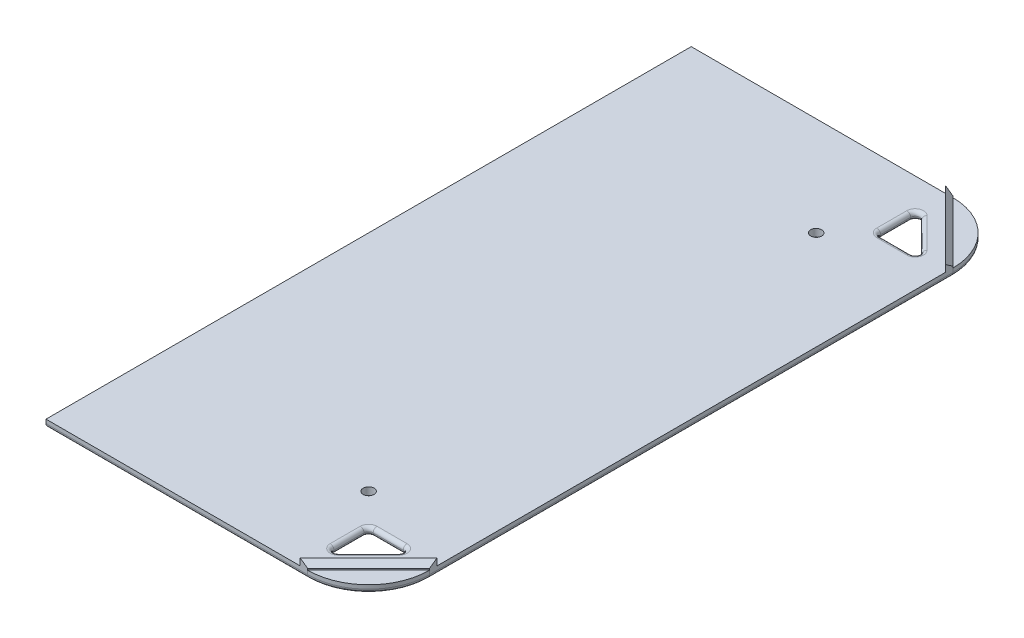
SolidWorks part; units mm, degrees
ref_plane "Front Plane" through (0, 0, 0) normal (0, 0, 1) x (1, 0, 0)
ref_plane "Top Plane" through (0, 0, 0) normal (0, 1, 0) x (1, 0, 0)
ref_plane "Right Plane" through (0, 0, 0) normal (1, 0, 0) x (0, 0, -1)
sketch "Sketch1" plane through (0, 0, 0) normal (0, 1, 0) x (1, 0, 0)
  line L0 (0, -134.62) -> (0, 134.62)
  line L1 (-134.62, -134.62) -> (134.62, -134.62)
  line L2 (-134.62, -134.62) -> (-134.62, 134.62)
  line L3 (-134.62, 134.62) -> (134.62, 134.62)
  line L4 (134.62, -134.62) -> (134.62, 134.62)
  line L5 (-134.62, -134.62) -> (134.62, 134.62) construction
  line L6 (-134.62, 134.62) -> (134.62, -134.62) construction
  point P0 (0, 0)
  point P9 (0, 0)
  dimension "D1" = 269.24
extrude "Boss-Extrude1" add sketch "Sketch1" along normal blind 3.175 contours L1 L4 L3 L0 region at (67.31, 0, 0)
sketch "Sketch2" plane through (0, 3.175, 0) normal (0, 1, 0) x (1, 0, 0)
  line L0 (109.22, 134.62) -> (134.62, 109.22)
  line L1 (109.22, 134.62) -> (106.045, 134.62)
  line L2 (106.045, 134.62) -> (134.62, 106.045)
  line L3 (134.62, 106.045) -> (134.62, 109.22)
  line L4 (0, -134.62) -> (134.62, -134.62)
  line L5 (134.62, -134.62) -> (134.62, 134.62)
  line L6 (134.62, 134.62) -> (0, 134.62)
  line L7 (0, 134.62) -> (0, -134.62)
  line L8 (0, -134.62) -> (134.62, -134.62)
  line L9 (134.62, -134.62) -> (134.62, 134.62)
  line L10 (134.62, 134.62) -> (0, 134.62)
  line L11 (0, 134.62) -> (0, -134.62)
  line L12 (109.22, -134.62) -> (134.62, -109.22)
  line L13 (134.62, -109.22) -> (134.62, -106.045)
  line L14 (134.62, -106.045) -> (106.045, -134.62)
  line L15 (106.045, -134.62) -> (109.22, -134.62)
  line L16 (120.3325, -120.3325) -> (115.3934, -115.3934)
  line L17 (120.3325, 120.3325) -> (115.3934, 115.3934)
  line L18 (105.8684, -124.9184) -> (124.9184, -105.8684)
  line L19 (124.9184, -105.8684) -> (105.8684, -105.8684)
  line L20 (105.8684, -105.8684) -> (105.8684, -124.9184)
  line L21 (124.9184, 105.8684) -> (105.8684, 124.9184)
  line L22 (105.8684, 124.9184) -> (105.8684, 105.8684)
  line L23 (105.8684, 105.8684) -> (124.9184, 105.8684)
  line L24 (120.3325, -120.3325) -> (93.3917, -93.3917)
  line L25 (120.3325, 120.3325) -> (93.3917, 93.3917)
  circle A0 centre (93.3917, -93.3917) radius 2.286
  circle A1 centre (93.3917, 93.3917) radius 2.286
  point P10 (120.3325, -120.3325)
  point P13 (120.3325, 120.3325)
  point P21 (115.3934, -115.3934)
  point P25 (115.3934, 115.3934)
  line M24 (134.62, -134.62) -> (134.62, 134.62)
  line M25 (134.62, 134.62) -> (0, 134.62)
  dimension "D17" = 4.572
  dimension "D2" = 3.175
  dimension "D3" = 25.4
  dimension "D4" = 3.175
  dimension "D5" = 25.4
  dimension "D6" = 3.175
  dimension "D7" = 3.175
  dimension "D8" = 25.4
  dimension "D9" = 6.985
  dimension "D10" = 90
  dimension "D11" = 6.985
  dimension "D12" = 90
  dimension "D13" = 19.05
  dimension "D14" = 19.05
  dimension "D15" = 38.1
  dimension "D16" = 90
  dimension "D18" = 90
  dimension "D1" = 0
extrude "Boss-Extrude2" add sketch "Sketch2" along normal blind 3.175 contours L2 L0 M25 M24 | L9 L14 L8 L12 region at (121.1107, 3.175, -121.1107) region at (121.1107, 3.175, 121.1107)
extrude "Cut-Extrude1" cut sketch "Sketch2<3>" against normal up to next contours L22 L23 L21 | A1 | L20 L18 L19 | A0
sketch "Sketch2<3>" plane through (0, 3.175, 0) normal (0, 1, 0) x (1, 0, 0) same geometry as "Sketch2"
chamfer "Chamfer1" distance 2.54 2 edges at (121.92, 6.35, 121.92) (121.92, 6.35, -121.92)
fillet "Fillet1" radius 1.905 6 edges at (105.8684, 1.5875, -105.8684) (124.9184, 1.5875, -105.8684) (105.8684, 1.5875, -124.9184) (105.8684, 1.5875, 105.8684) (105.8684, 1.5875, 124.9184) (124.9184, 1.5875, 105.8684)
fillet "Fillet2" radius 1.5875 24 edges at (107.0443, 3.175, 122.0793) (105.8684, 3.175, 114.0463) (106.4263, 3.175, 106.4263) (114.0463, 3.175, 105.8684) (122.0793, 3.175, 107.0443) (122.0793, 0, 107.0443) (114.0463, 0, 105.8684) (106.4263, 0, 106.4263) (105.8684, 0, 114.0463) (107.0443, 0, 122.0793) (122.0793, 3.175, -107.0443) (114.0463, 3.175, -105.8684) (106.4263, 3.175, -106.4263) (105.8684, 3.175, -114.0463) (107.0443, 3.175, -122.0793) (107.0443, 0, -122.0793) (105.8684, 0, -114.0463) (106.4263, 0, -106.4263) (114.0463, 0, -105.8684) (122.0793, 0, -107.0443) (115.3934, 3.175, 115.3934) (115.3934, 0, 115.3934) (115.3934, 3.175, -115.3934) (115.3934, 0, -115.3934)
fillet "Fillet3" radius 25.4 2 edges at (134.62, 1.5875, -134.62) (134.62, 1.5875, 134.62)
fillet "Fillet4" radius 1.5875 5 edges at (54.61, 0, 134.62) (127.1805, 0, 127.1805) (54.61, 0, -134.62) (127.1805, 0, -127.1805) (134.62, 0, 0)
sketch "Sketch3" plane through (0, 0, 0) normal (0, -1, 0) x (1, 0, 0)
  line L1 (0, -28.575) -> (31.75, -28.575)
  line L2 (0, -28.575) -> (0, 28.575)
  line L3 (0, 28.575) -> (31.75, 28.575)
  line L4 (109.22, 133.0325) -> (0, 133.0325)
  line L5 (0, 133.0325) -> (0, -133.0325)
  line L6 (0, -133.0325) -> (109.22, -133.0325)
  line L7 (133.0325, -109.22) -> (133.0325, 109.22)
  line L8 (109.22, 133.0325) -> (0, 133.0325)
  line L9 (0, 133.0325) -> (0, -133.0325)
  line L10 (0, -133.0325) -> (109.22, -133.0325)
  line L11 (133.0325, -109.22) -> (133.0325, 109.22)
  line L12 (31.75, -28.575) -> (31.75, 28.575)
  line L13 (0, 110.8075) -> (31.75, 110.8075)
  line L14 (0, 110.8075) -> (0, 53.6575)
  line L15 (0, 53.6575) -> (31.75, 53.6575)
  line L16 (31.75, 110.8075) -> (31.75, 53.6575)
  line L17 (0, -53.6575) -> (31.75, -53.6575)
  line L18 (0, -53.6575) -> (0, -110.8075)
  line L19 (0, -110.8075) -> (31.75, -110.8075)
  line L20 (31.75, -53.6575) -> (31.75, -110.8075)
  arc A2 (133.0325, 109.22) -> (109.22, 133.0325) centre (109.22, 109.22) ccw
  arc A3 (109.22, -133.0325) -> (133.0325, -109.22) centre (109.22, -109.22) ccw
  arc A4 (133.0325, 109.22) -> (109.22, 133.0325) centre (109.22, 109.22) ccw
  arc A5 (109.22, -133.0325) -> (133.0325, -109.22) centre (109.22, -109.22) ccw
  point P20 (0, 82.2325)
  point P21 (0, 0)
  point P22 (0, -82.2325)
  line M35 (0, 133.0325) -> (0, -133.0325)
  dimension "D2" = 57.15
  dimension "D3" = 31.75
  dimension "D4" = 50.8
  dimension "D5" = 50.8
  dimension "D1" = 0
extrude "Boss-Extrude3" add sketch "Sketch3" along normal blind 3.175 contours L16 L13 L9 L15 | L1 L12 L3 M35 | L20 L17 L9 L19 region at (15.875, 0, 0) region at (15.875, 0, -82.2325) region at (15.875, 0, 82.2325)
sketch "Sketch4" plane through (0, 0, 0) normal (-1, 0, 0) x (0, 0, 1)
  line L0 (110.8075, 0) -> (110.8075, 3.175)
  line L1 (110.8075, 3.175) -> (53.6575, 3.175)
  line L2 (53.6575, 3.175) -> (53.6575, 0)
  line L3 (28.575, 0) -> (28.575, 3.175)
  line L4 (28.575, 3.175) -> (-28.575, 3.175)
  line L5 (-28.575, 3.175) -> (-28.575, 0)
  line L6 (-53.6575, 0) -> (-53.6575, 3.175)
  line L7 (-53.6575, 3.175) -> (-110.8075, 3.175)
  line L8 (-110.8075, 3.175) -> (-110.8075, 0)
  line L9 (-53.6575, 3.175) -> (-110.8075, 3.175)
  line L10 (28.575, 3.175) -> (-28.575, 3.175)
  line L12 (-107.6325, 1.5875) -> (-56.8325, 1.5875)
  line L13 (-107.6325, 1.5875) -> (-107.6325, -1.5875)
  line L14 (-107.6325, -1.5875) -> (-56.8325, -1.5875)
  line L15 (-56.8325, 1.5875) -> (-56.8325, -1.5875)
  line L16 (110.8075, 0) -> (133.0325, 0)
  line L17 (134.62, 1.5875) -> (134.62, 3.175)
  line L18 (134.62, 3.175) -> (-134.62, 3.175)
  line L19 (-134.62, 3.175) -> (-134.62, 1.5875)
  line L20 (-133.0325, 0) -> (-110.8075, 0)
  line L21 (-110.8075, 0) -> (-110.8075, -3.175)
  line L22 (-110.8075, -3.175) -> (-53.6575, -3.175)
  line L23 (-53.6575, -3.175) -> (-53.6575, 0)
  line L24 (-53.6575, 0) -> (-28.575, 0)
  line L25 (-28.575, 0) -> (-28.575, -3.175)
  line L26 (-28.575, -3.175) -> (28.575, -3.175)
  line L27 (28.575, -3.175) -> (28.575, 0)
  line L28 (28.575, 0) -> (53.6575, 0)
  line L29 (53.6575, 0) -> (53.6575, -3.175)
  line L30 (53.6575, -3.175) -> (110.8075, -3.175)
  line L31 (110.8075, -3.175) -> (110.8075, 0)
  line L34 (110.8075, 3.175) -> (53.6575, 3.175)
  line L37 (-110.8075, 0) -> (-110.8075, -3.175)
  line L38 (-110.8075, -3.175) -> (-53.6575, -3.175)
  line L39 (-53.6575, -3.175) -> (-53.6575, 0)
  line L41 (-28.575, 0) -> (-28.575, -3.175)
  line L42 (-28.575, -3.175) -> (28.575, -3.175)
  line L43 (28.575, -3.175) -> (28.575, 0)
  line L45 (53.6575, 0) -> (53.6575, -3.175)
  line L46 (53.6575, -3.175) -> (110.8075, -3.175)
  line L47 (110.8075, -3.175) -> (110.8075, 0)
  line L48 (-107.6325, 1.5875) -> (-56.8325, -1.5875) construction
  line L49 (-107.6325, -1.5875) -> (-56.8325, 1.5875) construction
  line L50 (-25.4, 1.5875) -> (25.4, 1.5875)
  line L51 (-25.4, 1.5875) -> (-25.4, -1.5875)
  line L52 (-25.4, -1.5875) -> (25.4, -1.5875)
  line L53 (25.4, 1.5875) -> (25.4, -1.5875)
  line L54 (-25.4, 1.5875) -> (25.4, -1.5875) construction
  line L55 (-25.4, -1.5875) -> (25.4, 1.5875) construction
  line L56 (56.8325, 1.5875) -> (107.6325, 1.5875)
  line L57 (56.8325, 1.5875) -> (56.8325, -1.5875)
  line L58 (56.8325, -1.5875) -> (107.6325, -1.5875)
  line L59 (107.6325, 1.5875) -> (107.6325, -1.5875)
  line L60 (56.8325, 1.5875) -> (107.6325, -1.5875) construction
  line L61 (56.8325, -1.5875) -> (107.6325, 1.5875) construction
  arc A2 (133.0325, 0) -> (134.62, 1.5875) centre (133.0325, 1.5875) ccw
  arc A3 (-134.62, 1.5875) -> (-133.0325, 0) centre (-133.0325, 1.5875) ccw
  point P16 (82.2325, 3.175)
  point P18 (0, 3.175)
  point P20 (-82.2325, 3.175)
  point P22 (-82.2325, 0)
  point P32 (0, 0)
  point P40 (82.2325, 0)
  dimension "D2" = 50.8
  dimension "D3" = 3.175
  dimension "D1" = 0
extrude "Cut-Extrude2" cut sketch "Sketch4" against normal blind 19.05 contours L53 L50 L51 L52 | L59 L56 L57 L58 | L15 L12 L13 L14 region at (0, 0, -82.2325) region at (0, 0, 0) region at (0, 0, 82.2325)
fillet "Fillet5" radius 12.7 6 edges at (31.75, -1.5875, 110.8075) (31.75, -1.5875, 53.6575) (31.75, -1.5875, 28.575) (31.75, -1.5875, -28.575) (31.75, -1.5875, -53.6575) (31.75, -1.5875, -110.8075)
fillet "Fillet6" radius 3.175 15 edges at (9.525, -3.175, -110.8075) (28.0303, -3.175, -107.0878) (31.75, -3.175, -82.2325) (28.0303, -3.175, -57.3772) (9.525, -3.175, -28.575) (28.0303, -3.175, -24.8553) (31.75, -3.175, 0) (28.0303, -3.175, 24.8553) (9.525, -3.175, 53.6575) (28.0303, -3.175, 57.3772) (31.75, -3.175, 82.2325) (28.0303, -3.175, 107.0878) (9.525, -3.175, -53.6575) (9.525, -3.175, 28.575) (9.525, -3.175, 110.8075)
